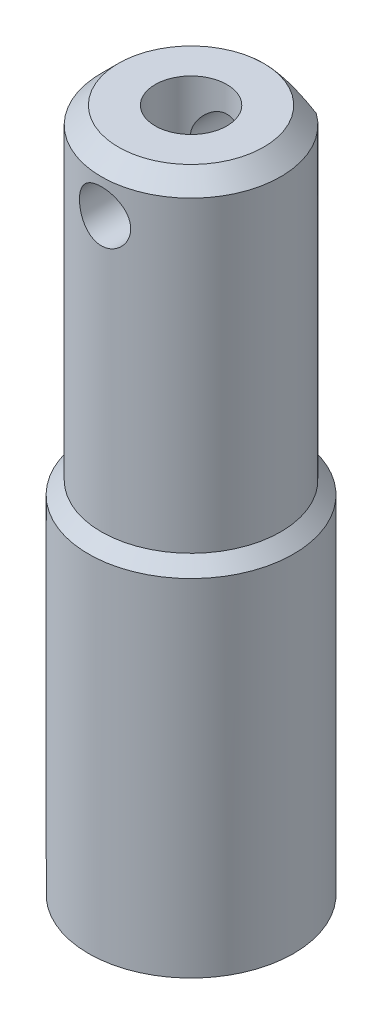
SolidWorks part; units mm, degrees
ref_plane "Front Plane" through (0, 0, 0) normal (0, 0, 1) x (1, 0, 0)
ref_plane "Top Plane" through (0, 0, 0) normal (0, 1, 0) x (1, 0, 0)
ref_plane "Right Plane" through (0, 0, 0) normal (1, 0, 0) x (0, 0, -1)
sketch "Sketch1" plane through (0, 0, 0) normal (0, 1, 0) x (1, 0, 0)
  circle A0 centre (0, 0) radius 6
  dimension "D1" = 12
extrude "Boss-Extrude1" add sketch "Sketch1" along normal blind 20
sketch "Sketch2" plane through (0, 20, 0) normal (0, 1, 0) x (1, 0, 0)
  circle A0 centre (0, 0) radius 5.25
  dimension "D1" = 10.5
extrude "Boss-Extrude2" add sketch "Sketch2" along normal blind 20
sketch "Sketch3" plane through (0, 40, 0) normal (0, 1, 0) x (1, 0, 0)
  line L0 (-3.0822, 4.25) -> (3.0822, 4.25)
  circle A0 centre (0, 0) radius 5.25 construction
  arc A1 (3.0822, 4.25) -> (-3.0822, 4.25) centre (0, 0) ccw
  dimension "D1" = 4.25
extrude "Cut-Extrude1" cut sketch "Sketch3" against normal blind 12
hole_wizard "M5 Tapped Hole1" positions "Sketch4" profile "Sketch5" tap size "M5" standard "ISO"
sketch "Sketch4" plane through (0, 40, 0) normal (0, 1, 0) x (1, 0, 0)
  point P0 (0, 0)
sketch "Sketch5" plane through (0, 40, 0) normal (1, 0, 0) x (0, 0, 1)
  line L0 (0, 0) -> (0, 15.2618)
  line L1 (0, 15.2618) -> (2.1, 14)
  line L2 (2.1, 14) -> (2.1, 0)
  line L5 (2.1, 0) -> (0, 0)
  line L10 (0, 15.2618) -> (-2.1, 14) construction
  line L11 (0, -6.35) -> (0, 107.95) construction
  dimension "Tap Drill Dia." = 4.2
  dimension "Tap Drill Depth" = 14
  dimension "Drill Angle" = 118
cosmetic thread "Hole Thread1" parameters "D1"=10, "D2"=5
sketch "Sketch6" plane through (0, 0, -4.25) normal (0, 0, -1) x (-1, 0, 0)
  line L0 (0, 40) -> (0, 28) construction
  line L1 (3.0822, 40) -> (-3.0822, 40) construction
  line L2 (3.0822, 28) -> (-3.0822, 28) construction
  circle A0 centre (0, 37) radius 1.5
  dimension "D1" = 3
  dimension "D2" = 3
extrude "Cut-Extrude2" cut sketch "Sketch6" against normal through all
chamfer "Chamfer1" distance 1 angle 45 2 edges at (0, 20, 5.25) (0, 40, 5.25)
